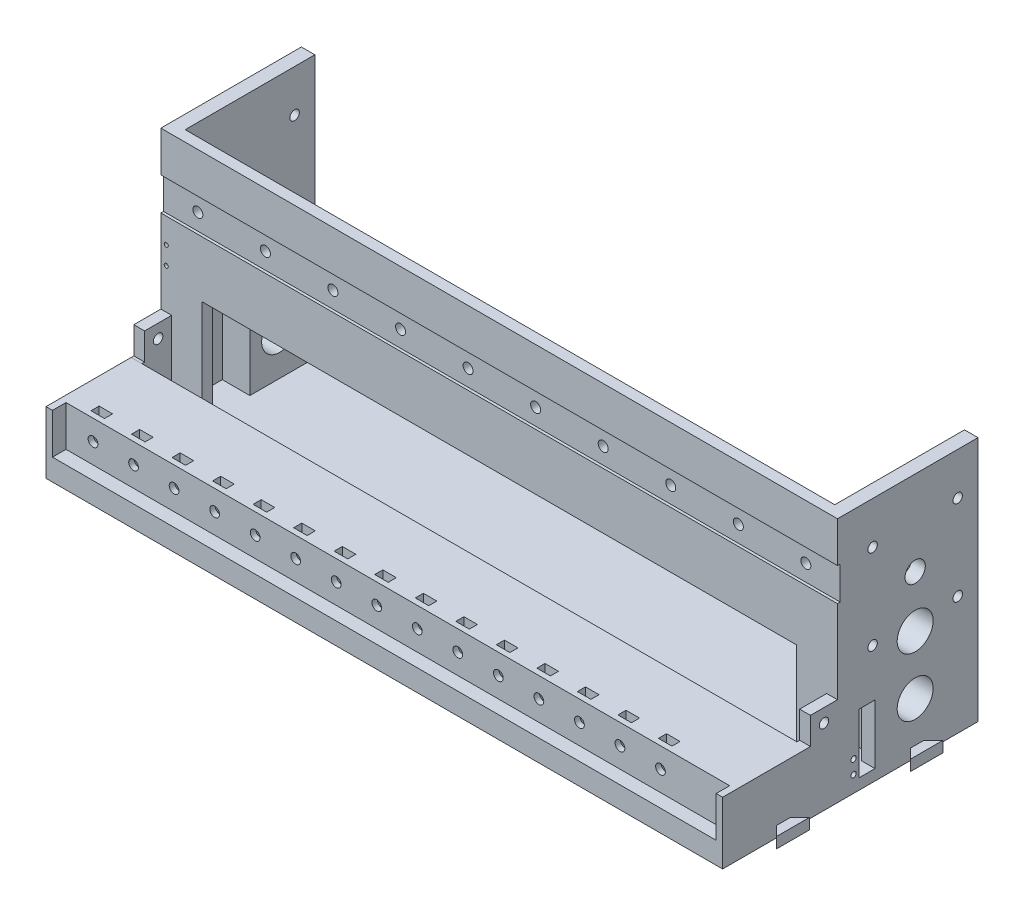
SolidWorks part; units mm, degrees
ref_plane "Front Plane" through (0, 0, 0) normal (0, 0, 1) x (1, 0, 0)
ref_plane "Top Plane" through (0, 0, 0) normal (0, 1, 0) x (1, 0, 0)
ref_plane "Right Plane" through (0, 0, 0) normal (1, 0, 0) x (0, 0, -1)
sketch "Sketch21" plane through (0, 0, 0) normal (0, 1, 0) x (1, 0, 0)
  line L1 (0, 0) -> (250.4, 0)
  line L2 (0, 0) -> (0, -94.5)
  line L3 (0, -94.5) -> (250.4, -94.5)
  line L4 (250.4, 0) -> (250.4, -94.5)
  dimension "D1" = 250.4
  dimension "D2" = 94.5
extrude "Base" add sketch "Sketch21" along normal blind 4
sketch "Sketch22" plane through (0, 4, 0) normal (0, 1, 0) x (1, 0, 0)
  line L1 (0, -52) -> (250.4, -52)
  line L2 (0, -52) -> (0, -48)
  line L3 (0, -48) -> (250.4, -48)
  line L4 (250.4, -52) -> (250.4, -48)
  line L7 (250.4, 0) -> (0, 0) construction
  dimension "D1" = 4
  dimension "D2" = 48
extrude "MainWall" add sketch "Sketch22" along normal blind 87
ref_plane "MiddlePlane" through (125.2, 0, 0) normal (-1, 0, 0) x (0, 0, 1)
sketch "Sketch2" plane through (0, 0, 52) normal (0, 0, 1) x (1, 0, 0)
  line L0 (0, 91) -> (0, 4) construction
  line L1 (250.4, 76) -> (0, 76)
  line L2 (250.4, 76) -> (250.4, 63.8)
  line L3 (250.4, 63.8) -> (0, 63.8)
  line L4 (0, 76) -> (0, 63.8)
  line L5 (0, 91) -> (250.4, 91) construction
  line L6 (250.4, 91) -> (250.4, 4) construction
  dimension "D1" = 12.2
  dimension "D3" = 15
extrude "RailCutout" cut sketch "Sketch2" against normal blind 1
sketch "Sketch6" plane through (0, 0, 52) normal (0, 0, 1) x (1, 0, 0)
  line L0 (0, 63.8) -> (250.4, 63.8) construction
  line L1 (235.2, 23) -> (15.2, 23)
  line L2 (235.2, 23) -> (235.2, 43)
  line L3 (235.2, 43) -> (15.2, 43)
  line L5 (125.2, 63.8) -> (125.2, 43) construction
  line L6 (0, 4) -> (250.4, 4) construction
  line L9 (15.2, 43) -> (15.2, 23)
  dimension "D1" = 20
  dimension "D2" = 19
  dimension "D3" = 220
extrude "PaperChannel" cut sketch "Sketch6" against normal blind 5
sketch "Sketch3" plane through (0, 0, 51) normal (0, 0, 1) x (1, 0, 0)
  line L1 (250.4, 63.8) -> (250.4, 76) construction
  line L3 (237.7, 69.9) -> (250.4, 69.9) construction
  circle A0 centre (237.7, 69.9) radius 1.85
  dimension "D1" = 12.7
  dimension "D2" = 3.7
extrude "RailScrewHole" cut sketch "Sketch3" against normal blind 4
pattern_linear "RailScrewPattern" count 10 spacing 25 along (-1, 0, 0) of "RailScrewHole"
sketch "Sketch13" plane through (0, 0, 0) normal (1, 0, 0) x (0, 0, -1)
  line L0 (0, 4) -> (0, 0) construction
  line L1 (-48, 91) -> (0, 91)
  line L2 (-48, 91) -> (-48, 4)
  line L3 (-48, 4) -> (0, 4)
  line L4 (0, 91) -> (0, 4)
  line L6 (-48, 91) -> (-48, 4) construction
  line L7 (0, 4) -> (-48, 4) construction
  dimension "D2" = 87
extrude "YWall" add sketch "Sketch13" along normal blind 5
sketch "Sketch20" plane through (0, 4, 0) normal (0, 1, 0) x (1, 0, 0)
  line L0 (250.4, -94.5) -> (250.4, -52) construction
  line L1 (250.4, -52) -> (0, -52)
  line L2 (250.4, -52) -> (250.4, -94.5)
  line L3 (250.4, -94.5) -> (0, -94.5)
  line L4 (0, -52) -> (0, -94.5)
  line L5 (0, -52) -> (0, -94.5) construction
  line L8 (0, -52) -> (250.4, -52) construction
  dimension "D2" = 42.5
extrude "BaseExtension" add sketch "Sketch20" along normal blind 19
sketch "Sketch14" plane through (0, 0, 0) normal (1, 0, 0) x (0, 0, -1)
  line L0 (-23.25, 40.65) -> (-23.25, 19) construction
  line L1 (-48, 4) -> (0, 4) construction
  line L2 (-23.25, 40.65) -> (-23.25, 59.65) construction
  line L3 (-39, 75.4) -> (-7.5, 75.4) construction
  line L4 (-39, 75.4) -> (-7.5, 43.9) construction
  line L5 (-7.5, 75.4) -> (-39, 43.9) construction
  line L6 (-39, 43.9) -> (-7.5, 43.9) construction
  line L7 (-48, 91) -> (-48, 4) construction
  circle A0 centre (-23.25, 19) radius 6.65
  circle A1 centre (-23.25, 40.65) radius 6.65
  circle A2 centre (-23.25, 59.65) radius 3.75
  circle A3 centre (-7.5, 43.9) radius 1.75
  circle A4 centre (-7.5, 75.4) radius 1.75
  circle A5 centre (-39, 75.4) radius 1.75
  circle A6 centre (-39, 43.9) radius 1.75
  point P18 (-23.25, 59.65)
  dimension "D1" = 21.65
  dimension "D2" = 13.3
  dimension "D3" = 13.3
  dimension "D6" = 7.5
  dimension "D7" = 3.5
  dimension "D8" = 3.5
  dimension "D9" = 3.5
  dimension "D10" = 3.5
  dimension "D15" = 15
  dimension "D4" = 9
  dimension "D5" = 19
  dimension "D11" = 31.5
  dimension "D12" = 31.5
  dimension "D13" = 31.5
  dimension "D14" = 31.5
extrude "MotorScrewBearingHoles" cut sketch "Sketch14" along normal blind 5
mirror "MirrorYWallHoles" about plane through (125.2, 0, 0) normal (-1, 0, 0) of "MotorScrewBearingHoles", "YWall"
sketch "Sketch26" plane through (5, 0, 0) normal (1, 0, 0) x (0, 0, -1)
  line L0 (-23.25, 50.65) -> (-23.25, 4) construction
  line L1 (-34.25, 4) -> (-12.25, 4)
  line L2 (-34.25, 4) -> (-34.25, 43.15)
  line L3 (-26.75, 50.65) -> (-19.75, 50.65)
  line L4 (-12.25, 4) -> (-12.25, 43.15)
  line L6 (-48, 4) -> (0, 4) construction
  circle A0 centre (-23.25, 19) radius 6.65
  circle A1 centre (-23.25, 40.65) radius 6.65
  arc A2 (-34.25, 43.15) -> (-26.75, 50.65) centre (-26.75, 43.15) cw
  arc A3 (-19.75, 50.65) -> (-12.25, 43.15) centre (-19.75, 43.15) cw
  dimension "D1" = 10
  dimension "D2" = 7.5
  dimension "D3" = 22
extrude "LeftRollerOffset" add sketch "Sketch26" along normal blind 10.2
chamfer "Chamfer2" distance 15 angle 45 1 edges at (125.2, 23, 48)
sketch "Sketch28" plane through (245.4, 0, 0) normal (-1, 0, 0) x (0, 0, 1)
  line L0 (48, 4) -> (0, 4) construction
  line L1 (19.75, 50.65) -> (26.75, 50.65)
  line L2 (12.25, 43.15) -> (12.25, 4)
  line L3 (12.25, 4) -> (34.25, 4)
  line L4 (34.25, 43.15) -> (34.25, 4)
  line L5 (23.25, 4) -> (23.25, 50.65) construction
  circle A0 centre (23.25, 40.65) radius 6.65
  circle A2 centre (23.25, 19) radius 6.65
  arc A3 (19.75, 50.65) -> (12.25, 43.15) centre (19.75, 43.15) ccw
  arc A4 (26.75, 50.65) -> (34.25, 43.15) centre (26.75, 43.15) cw
  dimension "D1" = 10
  dimension "D3" = 7.5
  dimension "D2" = 22
extrude "RightRollerOffset" add sketch "Sketch28" along normal blind 10
sketch "Sketch29" plane through (0, 0, 0) normal (-1, 0, 0) x (0, 0, 1)
  line L0 (52, 23) -> (52, 33)
  line L1 (52, 63.8) -> (52, 12) construction
  line L3 (63, 23) -> (94.5, 23) construction
  line L5 (52, 33) -> (62, 33)
  line L6 (62, 33) -> (62, 23)
  line L7 (52, 33) -> (62, 23) construction
  line L8 (52, 23) -> (52, 12)
  line L9 (52, 12) -> (63, 23)
  line L10 (63, 23) -> (62, 23)
  line L11 (62, 23) -> (52, 23) construction
  circle A0 centre (57, 28) radius 1.75
  point P10 (57, 28)
  dimension "D3" = 3.5
  dimension "D1" = 10
  dimension "D2" = 10
extrude "BackMountScrew" add sketch "Sketch29" against normal blind 4 separate body
mirror "Mirror5" about plane through (125.2, 0, 0) normal (-1, 0, 0) of "BackMountScrew"
sketch "Sketch34" plane through (0, 0, 0) normal (0, -1, 0) x (1, 0, 0)
  line L0 (0, 64.75) -> (-3.5355, 68.2855)
  line L1 (0, 0) -> (0, 94.5) construction
  line L2 (-3.5355, 68.2855) -> (-3.5355, 56.2145)
  line L3 (-3.5355, 56.2145) -> (0, 59.75)
  line L4 (0, 59.75) -> (0, 64.75)
  line L5 (0, 47.25) -> (0, 62.25) construction
  line L6 (0, 47.25) -> (250.4, 47.25) construction
  line L7 (250.4, 94.5) -> (250.4, 0) construction
  line L9 (-3.5355, 38.2855) -> (0, 34.75)
  line L10 (-3.5355, 26.2145) -> (-3.5355, 38.2855)
  line L11 (0, 29.75) -> (-3.5355, 26.2145)
  line L12 (0, 34.75) -> (0, 29.75)
  dimension "D1" = 45
  dimension "D2" = 5
  dimension "D3" = 5
  dimension "D4" = 15
extrude "Dovetails_Left" add sketch "Sketch34" against normal blind 4
sketch "Sketch49" plane through (0, 0, 0) normal (0, -1, 0) x (1, 0, 0)
  line L0 (250.4, 74.5) -> (253.9355, 78.0355)
  line L1 (250.4, 94.5) -> (250.4, 0) construction
  line L2 (253.9355, 78.0355) -> (253.9355, 65.9645)
  line L3 (253.9355, 65.9645) -> (250.4, 69.5)
  line L4 (250.4, 69.5) -> (250.4, 74.5)
  line L5 (250.4, 47.25) -> (0, 47.25) construction
  line L6 (0, 0) -> (0, 94.5) construction
  line L7 (250.4, 25) -> (250.4, 20)
  line L8 (253.9355, 28.5355) -> (250.4, 25)
  line L9 (253.9355, 16.4645) -> (253.9355, 28.5355)
  line L10 (250.4, 20) -> (253.9355, 16.4645)
  dimension "D1" = 20
  dimension "D2" = 5
  dimension "D3" = 5
  dimension "D4" = 45
extrude "Dovetails_Right" add sketch "Sketch49" against normal blind 4
sketch "Sketch43" plane through (0, 0, 52) normal (0, 0, 1) x (1, 0, 0)
  line L0 (0, 91) -> (250.4, 91) construction
  line L1 (0, 63.8) -> (0, 12) construction
  circle A0 centre (2, 54.6) radius 0.75
  circle A1 centre (2, 47.9) radius 0.75
  dimension "D1" = 1.5
  dimension "D3" = 1.5
  dimension "D2" = 36.4
  dimension "D4" = 6.7
  dimension "D5" = 2
extrude "Endstop_Screw_Holes" cut sketch "Sketch43" against normal blind 4
sketch "Sketch44" plane through (5, 0, 0) normal (1, 0, 0) x (0, 0, -1)
  line L1 (-48, 4) -> (-34.25, 4) construction
  line L7 (-44.125, 4) -> (-38.125, 4)
  line L8 (-44.125, 4) -> (-44.125, 26)
  line L9 (-44.125, 26) -> (-38.125, 26)
  line L10 (-38.125, 4) -> (-38.125, 26)
  line L11 (-46.0625, 11) -> (-44.125, 11) construction
  line L12 (-46.0625, 11) -> (-48, 11) construction
  line L13 (-48, 91) -> (-48, 4) construction
  line L14 (-46.0625, 11) -> (-46.0625, 6) construction
  circle A0 centre (-46.0625, 11) radius 1
  circle A1 centre (-46.0625, 6) radius 1
  point P6 (-41.125, 4)
  point P7 (-41.125, 4)
  dimension "D3" = 2
  dimension "D4" = 2
  dimension "D1" = 22
  dimension "D2" = 6
  dimension "D5" = 5
  dimension "D6" = 2
extrude "Cable_Passthrough" cut sketch "Sketch44" against normal up to next (5 mm away)
mirror "Cabble_Passthrough_Mirror" about plane through (125.2, 0, 0) normal (-1, 0, 0) of "Cable_Passthrough"
sketch "Sketch46" plane through (0, 23, 0) normal (0, 1, 0) x (1, 0, 0)
  line L0 (0, -94.5) -> (250.4, -94.5) construction
  line L1 (2.4, -89.5) -> (248, -89.5)
  line L2 (2.4, -89.5) -> (2.4, -94.5)
  line L3 (2.4, -94.5) -> (248, -94.5)
  line L4 (248, -89.5) -> (248, -94.5)
  line L5 (125.2, 50.05) -> (125.2, -50.05) construction
  point P6 (125.2, -94.5)
  dimension "D1" = 5
  dimension "D2" = 245.6
extrude "Channel_Cutout" cut sketch "Sketch46" against normal blind 15
sketch "Sketch47" plane through (0, 0, 89.5) normal (0, 0, 1) x (1, 0, 0)
  line L1 (2.4, 8) -> (2.4, 23) construction
  line L2 (248, 23) -> (2.4, 23) construction
  circle A0 centre (12.4, 15.5) radius 1.8
  dimension "D1" = 3.6
  dimension "D2" = 10
  dimension "D3" = 7.5
extrude "Channel_Screw_Hole" cut sketch "Sketch47" against normal blind 4
sketch "Sketch48" plane through (0, 23, 0) normal (0, 1, 0) x (1, 0, 0)
  line L0 (2.4, -89.5) -> (2.4, -94.5) construction
  line L1 (9.65, -84.5) -> (14.65, -84.5)
  line L2 (9.65, -84.5) -> (9.65, -87.5)
  line L3 (9.65, -87.5) -> (14.65, -87.5)
  line L4 (14.65, -84.5) -> (14.65, -87.5)
  line L5 (248, -89.5) -> (2.4, -89.5) construction
  dimension "D1" = 3
  dimension "D2" = 5
  dimension "D3" = 7.25
  dimension "D4" = 2
extrude "Channel_Nut_Hole" cut sketch "Sketch48" against normal blind 11.3
pattern_linear "LPattern1" count 15 spacing 15 along (1, 0, 0) of "Channel_Screw_Hole", "Channel_Nut_Hole"
equation "\"45.5.00mm\"=10"
equation "\"14.5.00mm\"=15"
